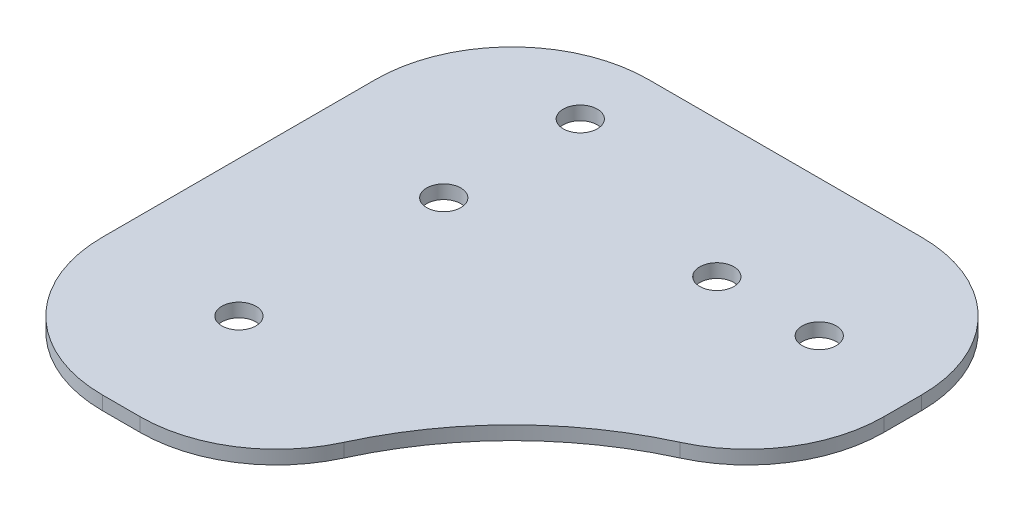
SolidWorks part; units mm, degrees
ref_plane "Plan de face" through (0, 0, 0) normal (0, 0, 1) x (1, 0, 0)
ref_plane "Plan de dessus" through (0, 0, 0) normal (0, 1, 0) x (1, 0, 0)
ref_plane "Plan de droite" through (0, 0, 0) normal (1, 0, 0) x (0, 0, -1)
sketch "Sketch1" plane through (0, 0, 0) normal (0, 1, 0) x (1, 0, 0)
  line L1 (80, 40) -> (0, 40)
  line L2 (80, 40) -> (80, 0)
  line L3 (80, 0) -> (0, 0)
  line L4 (0, 40) -> (0, 0)
  line L5 (0, 0) -> (40, 0)
  line L6 (0, 0) -> (0, -40)
  line L7 (0, -40) -> (40, -40)
  line L8 (40, 0) -> (40, -40)
  circle A0 centre (20, 10) radius 2.5
  circle A1 centre (65, 20) radius 2.5
  circle A2 centre (50, 20) radius 2.5
  circle A3 centre (20, 30) radius 2.5
  circle A8 centre (20, -20) radius 2.5
  point P15 (0, 20)
  point P30 (20, -40)
  point P32 (0, -20)
  dimension "D3" = 5
  dimension "D4" = 5
  dimension "D5" = 5
  dimension "D9" = 5
  dimension "D14" = 5
  dimension "D1" = 40
  dimension "D2" = 80
  dimension "D6" = 20
  dimension "D7" = 10
  dimension "D8" = 15
  dimension "D10" = 10
  dimension "D12" = 40
  dimension "D13" = 40
extrude "Boss-Extrude1" add sketch "Sketch1" along normal blind 2 contours L1 L4 L3 L2 A3 A2 A1 A0 | L8 L3 L6 L7 region at (40.0315, 0, -20) region at (20, 0, 0.5657)
fillet "Fillet1" radius 50 1 edges at (40, 1, 0)
fillet "Fillet2" radius 20 5 edges at (0, 1, -40) (80, 1, -40) (80, 1, 0) (40, 1, 40) (0, 1, 40)
